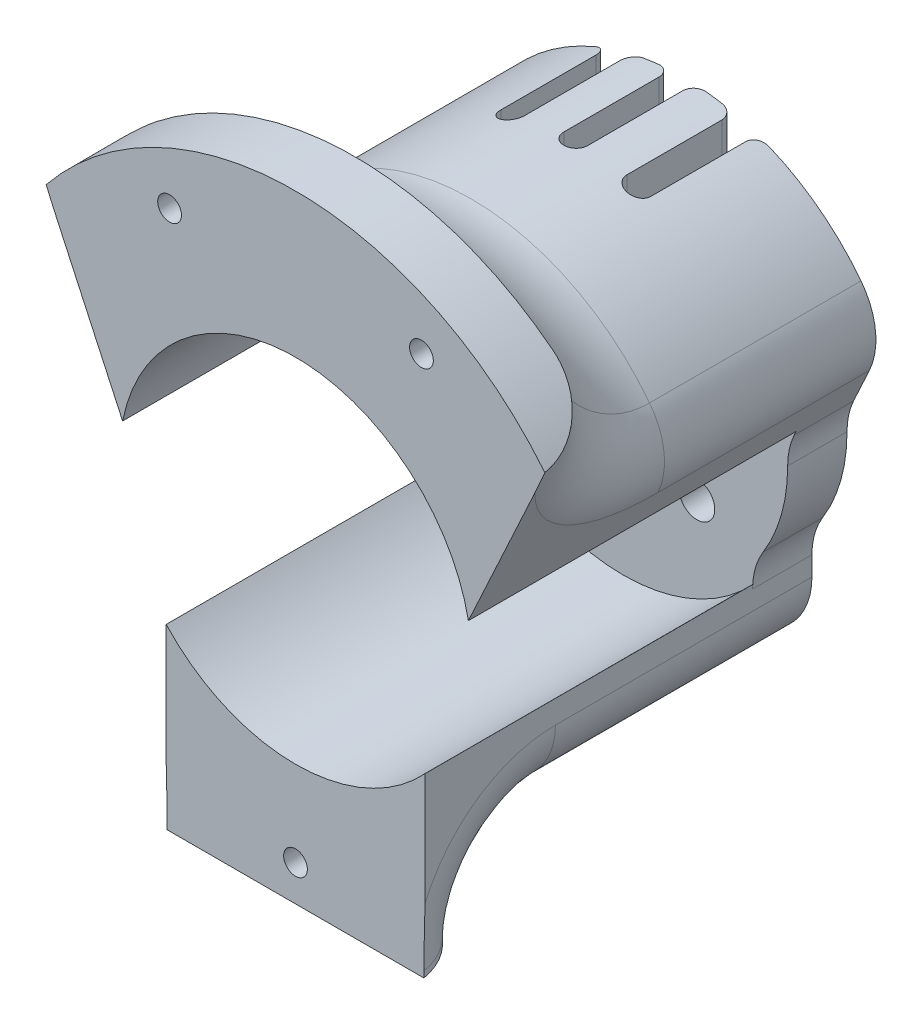
SolidWorks part; units mm, degrees
ref_plane "Front Plane" through (0, 0, 0) normal (0, 0, 1) x (1, 0, 0)
ref_plane "Top Plane" through (0, 0, 0) normal (0, 1, 0) x (1, 0, 0)
ref_plane "Right Plane" through (0, 0, 0) normal (1, 0, 0) x (0, 0, -1)
sketch "Sketch1" plane through (0, 0, 0) normal (0, 0, 1) x (1, 0, 0)
  line L1 (6.2099, -6.2099) -> (-6.2099, -6.2099) construction
  line L2 (6.2099, -6.2099) -> (6.2099, 6.2099) construction
  line L3 (6.2099, 6.2099) -> (-6.2099, 6.2099) construction
  line L4 (-6.2099, -6.2099) -> (-6.2099, 6.2099) construction
  line L5 (6.2099, -6.2099) -> (-6.2099, 6.2099) construction
  line L6 (6.2099, 6.2099) -> (-6.2099, -6.2099) construction
  circle A0 centre (0, 0) radius 13.85
  circle A1 centre (-6.2099, 6.2099) radius 1
  circle A2 centre (-6.2099, -6.2099) radius 1
  circle A3 centre (6.2099, -6.2099) radius 1
  circle A4 centre (6.2099, 6.2099) radius 1
  circle A5 centre (0, 0) radius 2.8
  dimension "D1" = 27.7
  dimension "D3" = 2
  dimension "D4" = 5.6
  dimension "D2" = 12.4197
extrude "Boss-Extrude1" add sketch "Sketch1" along normal blind 5
sketch "Sketch3" plane through (0, 0, 0) normal (0, 0, -1) x (-1, 0, 0)
  line L0 (-6.2099, -6.2099) -> (-6.2099, 6.2099) construction
ref_axis "Axis1" through (6.2099, 17.0042, 0) along (0, -1, 0)
sketch "Sketch4" plane through (0, 0, 0) normal (0, 0, -1) x (-1, 0, 0)
  line L2 (11.8156, -3.0368) -> (22.6956, 20.5161) construction
  line L3 (-22.6956, 20.5161) -> (-11.8156, -3.0368) construction
  line L4 (13.7939, 1.2457) -> (17.0714, 8.3408)
  line L5 (-17.0714, 8.3408) -> (-13.7939, 1.2457)
  arc A1 (17.0714, 8.3408) -> (-17.0714, 8.3408) centre (0, 0) ccw
  circle A2 centre (0, 0) radius 13.85 construction
  arc A3 (13.7939, 1.2457) -> (-13.7939, 1.2457) centre (0, 0) ccw
  dimension "D1" = 38
extrude "Boss-Extrude2" add sketch "Sketch4" against normal up to surface (32.6 mm away)
sketch "Sketch5" plane through (0, 0, 32.6) normal (0, 0, -1) x (-1, 0, 0)
  line L0 (10.6066, 20.3934) -> (0, 0) construction
  line L1 (10.6066, 20.3934) -> (12.4462, 23.9304) construction
  line L2 (10.6066, 20.3934) -> (4.3808, 23.6314) construction
  line L3 (4.3808, 23.6314) -> (8.767, 16.8564) construction
  line L4 (4.3808, 23.6314) -> (12.4462, 23.9304) construction
  line L5 (-22.6956, 20.5161) -> (-11.8156, -3.0368) construction
  line L6 (-21.0243, 16.8982) -> (-17.0714, 8.3408)
  line L7 (11.8156, -3.0368) -> (22.6956, 20.5161) construction
  line L8 (17.0714, 8.3408) -> (21.0243, 16.8982)
  arc A0 (21.0243, 16.8982) -> (-21.0243, 16.8982) centre (0, 0) ccw
  arc A1 (17.0714, 8.3408) -> (-17.0714, 8.3408) centre (0, 0) ccw construction
  arc A2 (17.0714, 8.3408) -> (-17.0714, 8.3408) centre (0, 0) ccw
  circle A3 centre (-10.6066, 20.3934) radius 1 construction
  circle A4 centre (10.6066, 20.3934) radius 1 construction
  circle A5 centre (-10.6066, 20.3934) radius 1
  circle A6 centre (10.6066, 20.3934) radius 1
extrude "Boss-Extrude3" add sketch "Sketch5" along normal blind 5
sketch "Sketch6" plane through (0, 0, 27.6) normal (0, 0, -1) x (-1, 0, 0)
  circle A0 centre (-10.6066, 20.3934) radius 2
  circle A1 centre (10.6066, 20.3934) radius 2
  dimension "D1" = 4
extrude "Cut-Extrude1" cut sketch "Sketch6" against normal blind 3
fillet "Fillet1" radius 10 1 edges at (0, 19, 27.6)
sketch "Sketch7" plane through (0, 0, 0) normal (0, 0, -1) x (-1, 0, 0)
  line L0 (10.8939, -25.0323) -> (10.8939, -7.2303) construction
  line L1 (-10.8939, -7.2303) -> (-10.8939, -25.0323) construction
  line L2 (10.8939, -15.5667) -> (10.8939, -8.5526)
  line L3 (-10.8939, -8.5526) -> (-10.8939, -15.5667)
  arc A0 (-10.8939, -15.5667) -> (10.8939, -15.5667) centre (0, 0) ccw
  arc A1 (17.0714, 8.3408) -> (-17.0714, 8.3408) centre (0, 0) ccw construction
  arc A2 (-13.7939, 1.2457) -> (13.7939, 1.2457) centre (0, 0) ccw construction
  arc A3 (-10.8939, -8.5526) -> (10.8939, -8.5526) centre (0, 0) ccw
extrude "Boss-Extrude4" add sketch "Sketch7" against normal up to surface (32.6 mm away)
sketch "Sketch8" plane through (0, 0, 32.6) normal (0, 0, -1) x (-1, 0, 0)
  line L0 (-10.8939, -15.5667) -> (-10.8939, -25.0323)
  line L1 (-10.8939, -25.0323) -> (10.8939, -25.0323)
  line L2 (10.8939, -25.0323) -> (10.8939, -15.5667)
  line L3 (0, -19) -> (0, -25.0323) construction
  line L4 (0, -25.0323) -> (0, -22.0161) construction
  arc A0 (-10.8939, -15.5667) -> (10.8939, -15.5667) centre (0, 0) ccw construction
  arc A1 (-10.8939, -15.5667) -> (10.8939, -15.5667) centre (0, 0) ccw
  circle A2 centre (0, -22.0161) radius 1
  dimension "D1" = 2
extrude "Boss-Extrude5" add sketch "Sketch8" along normal blind 5
sketch "Sketch9" plane through (0, 0, 27.6) normal (0, 0, -1) x (-1, 0, 0)
  circle A0 centre (0, -22.0161) radius 2
  dimension "D1" = 4
extrude "Cut-Extrude2" cut sketch "Sketch9" against normal blind 3
fillet "Fillet2" radius 6 1 edges at (0, -19, 27.6)
fillet "Fillet3" radius 6 14 edges at (17.8903, 10.1136, 23.1569) (10.8939, -23.7669, 27.6) (10.8939, -17.7797, 25.935) (-10.8939, -23.7669, 27.6) (-10.8939, -16.7498, 24.8875) (-17.9693, 10.2848, 23.3917) (17.0714, 8.3408, 8.9037) (10.8939, -15.5667, 10.8) (-10.8939, -15.5667, 10.8) (-17.0714, 8.3408, 8.9037) (-10.8939, -8.5526, 2.5) (-13.7939, 1.2457, 2.5) (10.8939, -8.5526, 2.5) (13.7939, 1.2457, 2.5)
sketch "Sketch10" plane through (0, 0, 0) normal (0, 0, -1) x (-1, 0, 0)
  line L0 (-6.3119, 11.0786) -> (0, 0) construction
  line L3 (-6.3119, 11.0786) -> (-4.3119, 11.0786)
  line L4 (-4.3119, 17.9209) -> (-4.3119, 11.0786)
  line L5 (-1, 19.4264) -> (1, 19.4264)
  line L6 (-1, 19.4264) -> (-1, 11.0786)
  line L7 (-1, 11.0786) -> (1, 11.0786)
  line L8 (1, 19.4264) -> (1, 11.0786)
  line L11 (4.3119, 11.0786) -> (6.3119, 11.0786)
  line L12 (6.3119, 18.5042) -> (6.3119, 11.0786)
  line L13 (0, 0) -> (6.3119, 11.0786) construction
  line L14 (0, 0) -> (0, 38.0039) construction
  line L15 (-1, 19.4264) -> (0, 11.0786) construction
  line L16 (0, 11.0786) -> (1, 19.4264) construction
  line L17 (-6.3119, 11.0786) -> (-6.3119, 19.4264)
  line L18 (-6.3119, 19.4264) -> (-4.3119, 19.4264)
  line L19 (-4.3119, 19.4264) -> (-4.3119, 17.9209)
  line L20 (4.3119, 11.0786) -> (4.3119, 19.4264)
  line L21 (4.3119, 19.4264) -> (6.3119, 19.4264)
  line L22 (6.3119, 19.4264) -> (6.3119, 18.5042)
extrude "Cut-Extrude3" cut sketch "Sketch10" against normal blind 10
fillet "Fillet4" radius 1 12 edges at (-6.3119, 14.4998, 0) (6.3119, 14.4998, 0) (4.3119, 14.7914, 0) (1, 15.0261, 0) (-1, 15.0261, 0) (-4.3119, 14.7914, 0) (-6.3119, 15.1245, 10) (-4.3119, 15.833, 10) (-1, 16.3938, 10) (1, 16.3938, 10) (6.3119, 15.1245, 10) (4.3119, 15.833, 10)
sketch "Sketch11" plane through (0, 0, 32.6) normal (0, 0, 1) x (1, 0, 0)
  circle A0 centre (0, 0) radius 14.85
  arc A1 (-6.3119, 12.3281) -> (-13.7939, 1.2457) centre (0, 0) ccw construction
  dimension "D1" = 1
extrude "Cut-Extrude4" cut sketch "Sketch11" against normal up to surface (27.6 mm away) up to face at (0, 4.0417, 5)
sketch "Sketch12" plane through (0, 0, 0) normal (0, 0, -1) x (-1, 0, 0)
  circle A0 centre (-6.2099, 6.2099) radius 1.5
  circle A1 centre (6.2099, 6.2099) radius 1.5
  circle A2 centre (6.2099, -6.2099) radius 1.5
  circle A3 centre (-6.2099, -6.2099) radius 1.5
  point P12 (0, 0)
  dimension "D1" = 3
  dimension "D2" = 4
extrude "Cut-Extrude5" cut sketch "Sketch12" against normal up to next
